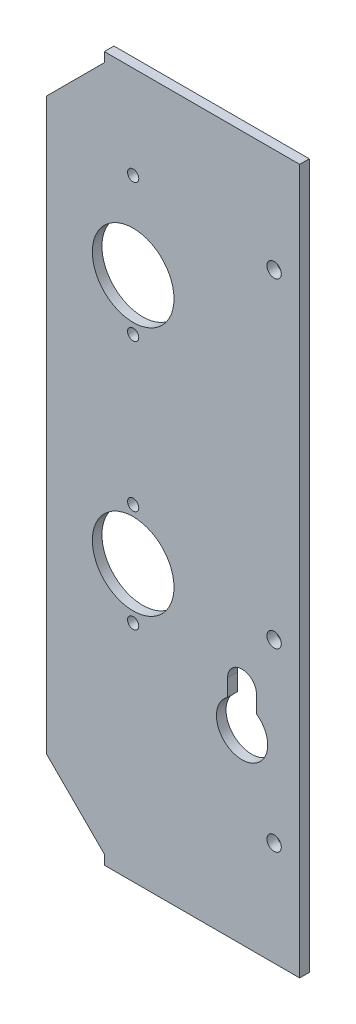
SolidWorks part; units mm, degrees
ref_plane "Front Plane" through (0, 0, 0) normal (0, 0, 1) x (1, 0, 0)
ref_plane "Top Plane" through (0, 0, 0) normal (0, 1, 0) x (1, 0, 0)
ref_plane "Right Plane" through (0, 0, 0) normal (1, 0, 0) x (0, 0, -1)
sketch "Sketch1" plane through (0, 0, 0) normal (0, 0, 1) x (1, 0, 0)
  line L0 (0, 110) -> (0, -110)
  line L1 (0, -110) -> (-61, -110)
  line L2 (-61, -110) -> (-61, -107)
  line L3 (-61, -107) -> (-79, -89)
  line L4 (-79, -89) -> (-79, 89)
  line L5 (-79, 89) -> (-61, 107)
  line L6 (-61, 107) -> (-61, 110)
  line L7 (-61, 110) -> (0, 110)
  dimension "D1" = 220
  dimension "D2" = 61
  dimension "D3" = 3
  dimension "D4" = 45
  dimension "D5" = 18
extrude "Boss-Extrude1" add sketch "Sketch1" against normal blind 3
sketch "Sketch2" plane through (0, 0, 0) normal (0, 0, 1) x (1, 0, 0)
  line L0 (-52, -24) -> (-52, 54) construction
  line L1 (-52, 15) -> (-79, 15) construction
  line L2 (0, 110) -> (-61, 110) construction
  line L3 (0, -110) -> (0, 110) construction
  line L4 (-79, 89) -> (-79, -89) construction
  circle A0 centre (-52, 54) radius 12.75
  circle A1 centre (-52, -24) radius 12.75
  dimension "D3" = 25.5
  dimension "D1" = 56
  dimension "D2" = 52
  dimension "D4" = 134
extrude "Cut-Extrude1" cut sketch "Sketch2" against normal through all
sketch "Sketch3" plane through (0, 0, -3) normal (0, 0, -1) x (-1, 0, 0)
  line L0 (52, 38) -> (52, 81) construction
  line L1 (52, 54) -> (26.162, 54) construction
  line L2 (52, -8) -> (52, -40) construction
  line L3 (52, -24) -> (42.2355, -24) construction
  circle A0 centre (52, 81) radius 1.75
  circle A1 centre (52, 38) radius 1.75
  circle A2 centre (52, -24) radius 12.75 construction
  circle A3 centre (52, 54) radius 12.75 construction
  circle A4 centre (52, -40) radius 1.75
  circle A5 centre (52, -8) radius 1.75
  dimension "D3" = 3.5
  dimension "D1" = 43
  dimension "D2" = 16
  dimension "D4" = 16
  dimension "D5" = 32
extrude "Cut-Extrude2" cut sketch "Sketch3" against normal through all
sketch "Sketch4" plane through (0, 0, 0) normal (0, 0, 1) x (1, 0, 0)
  line L0 (-8, 77.5) -> (-8, -77.5) construction
  line L1 (-8, 0) -> (0, 0) construction
  line L2 (0, -110) -> (0, 110) construction
  circle A0 centre (-8, 77.5) radius 2.25
  circle A1 centre (-8, -77.5) radius 2.25
  circle A2 centre (-8, -22.5) radius 2.25
  dimension "D1" = 155
  dimension "D3" = 4.5
  dimension "D4" = 55
  dimension "D2" = 8
extrude "Cut-Extrude3" cut sketch "Sketch4" against normal through all
sketch "Sketch5" plane through (0, 0, 0) normal (0, 0, 1) x (1, 0, 0)
  line L0 (-22.5, -40) -> (-22.5, -45.3856)
  line L1 (-13.5, -40) -> (-13.5, -45.3856)
  line L2 (-18, -40) -> (-18, -52) construction
  line L3 (0, -110) -> (0, 110) construction
  arc A0 (-22.5, -45.3856) -> (-13.5, -45.3856) centre (-18, -52) ccw
  arc A1 (-13.5, -40) -> (-22.5, -40) centre (-18, -40) ccw
  circle A2 centre (-8, -77.5) radius 2.25 construction
  dimension "D1" = 9
  dimension "D2" = 8
  dimension "D3" = 12
  dimension "D4" = 18
  dimension "D5" = 37.5
extrude "Cut-Extrude4" cut sketch "Sketch5" against normal through all
